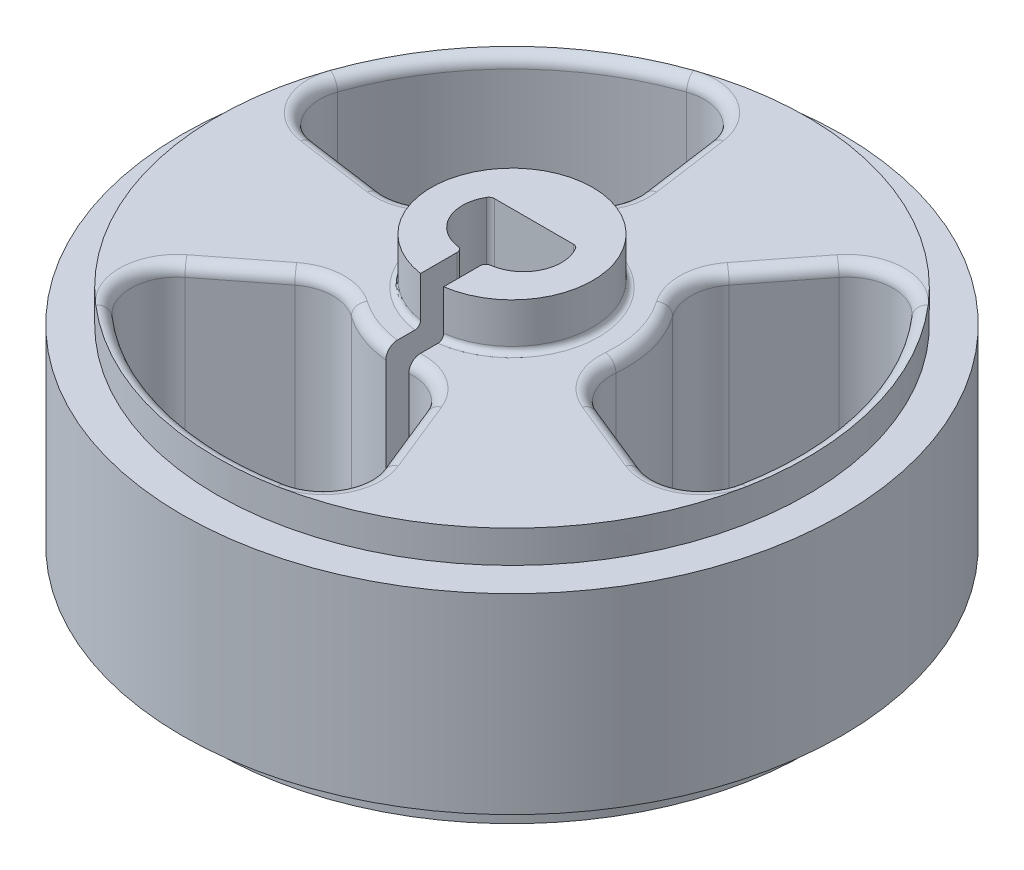
SolidWorks part; units mm, degrees
material "Nylon 101"
ref_plane "Front" through (0, 0, 0) normal (0, 0, 1) x (1, 0, 0)
ref_plane "Top" through (0, 0, 0) normal (0, 1, 0) x (1, 0, 0)
ref_plane "Right" through (0, 0, 0) normal (1, 0, 0) x (0, 0, -1)
sketch "Sketch1" plane through (0, 0, 0) normal (1, 0, 0) x (0, 0, -1)
  line L0 (0, 7.6229) -> (0, -6.4854) construction
  line L1 (0, -6.55) -> (12.8, -6.55)
  line L2 (12.8, -6.55) -> (12.8, -5.15)
  line L3 (12.8, -5.15) -> (14.3, -5.15)
  line L4 (14.3, -5.15) -> (14.3, 3.15)
  line L5 (14.3, 3.15) -> (12.8, 3.15)
  line L6 (12.8, 3.15) -> (12.8, 4.55)
  line L7 (12.8, 4.55) -> (3.5, 4.55)
  line L8 (3.5, 4.55) -> (3.5, 6.55)
  line L9 (3.5, 6.55) -> (0, 6.55)
  line L10 (0, -6.55) -> (0, 6.55)
  point P14 (0, 0)
  dimension "D1" = 11.1
  dimension "D2" = 8.3
  dimension "D3" = 7
  dimension "D4" = 2
  dimension "D5" = 14.3
  dimension "D6" = 1.5
revolve "Revolve1" add sketch "Sketch1" angle 360 about L0
sketch "Sketch2" plane through (0, 4.55, 0) normal (0, 1, 0) x (1, 0, 0)
  line L0 (0, 22.4874) -> (0, -21.7034) construction
  line L1 (-16.3723, 0) -> (20.3716, 0) construction
  line L2 (-1.7118, 12.1803) -> (-0.6959, 4.9513)
  line L3 (-12.1803, 1.7118) -> (-4.9513, 0.6959)
  arc A1 (-12.1803, 1.7118) -> (-1.7118, 12.1803) centre (0, 0) cw
  circle A2 centre (0, 0) radius 5
  arc A3 (-0.6959, 4.9513) -> (-4.9513, 0.6959) centre (0, 0) ccw
  circle A4 centre (0, 0) radius 12.8 construction
  dimension "D2" = 0.5
  dimension "D3" = 8
  dimension "D4" = 8
  dimension "D1" = 1.5
extrude "Cut-Extrude1" cut sketch "Sketch2" against normal through all
fillet "Fillet1" radius 2 4 edges at (-4.9513, -1, -0.6959) (-0.6959, -1, -4.9513) (-12.1803, -1, -1.7118) (-1.7118, -1, -12.1803)
fillet "Fillet2" radius 0.5 16 edges at (-11.4344, 4.55, -2.3447) (-8.6974, 4.55, -8.6974) (-2.3447, 4.55, -11.4344) (-1.1699, 4.55, -8.3243) (-1.1598, 4.55, -5.4042) (-3.5355, 4.55, -3.5355) (-5.4042, 4.55, -1.1598) (-8.3243, 4.55, -1.1699) (-1.1598, -6.55, -5.4042) (-3.5355, -6.55, -3.5355) (-5.4042, -6.55, -1.1598) (-8.3243, -6.55, -1.1699) (-11.4344, -6.55, -2.3447) (-8.6974, -6.55, -8.6974) (-2.3447, -6.55, -11.4344) (-1.1699, -6.55, -8.3243)
ref_axis "Axis1" through (0, 50, 0) along (0, -1, 0)
pattern_circular "CirPattern1" count 3 over 360 about axis through (0, 50, 0) along (0, -1, 0) of "Cut-Extrude1", "Fillet1", "Fillet2"
sketch "Sketch3" plane through (0, 6.55, 0) normal (0, 1, 0) x (1, 0, 0)
  line L0 (0, 0) -> (0, 1.9) construction
  line L1 (-0.5, -5.65) -> (-0.5, -1.65)
  line L2 (-1.8491, 0.95) -> (1.8491, 0.95)
  line L3 (0.5, -5.65) -> (0.5, -1.65)
  line L5 (-0.5, -5.65) -> (0.5, -5.65)
  arc A0 (-2.8963, -4.0757) -> (0.4704, -4.9778) centre (0, 0) ccw construction
  arc A1 (-2.8963, -4.0757) -> (0.4704, -4.9778) centre (0, 0) ccw construction
  arc A2 (-0.5, -1.65) -> (-1.8491, 0.95) centre (-0.5, 0) cw
  arc A3 (0.5, -1.65) -> (1.8491, 0.95) centre (0.5, 0) ccw
  point P15 (0, 0.95)
  dimension "D2" = 1.65
  dimension "D1" = 2.6
  dimension "D3" = 0.5
  dimension "D4" = 4
  dimension "D5" = 0.5
extrude "Cut-Extrude3" cut sketch "Sketch3" against normal through all
fillet "Fillet3" radius 0.25 4 edges at (0.5, 0, 1.65) (-0.5, 0, 1.65) (-1.8491, 0, -0.95) (1.8491, 0, -0.95)
fillet "Fillet4" radius 0.25 1 edges at (0, 4.55, -3.5)
